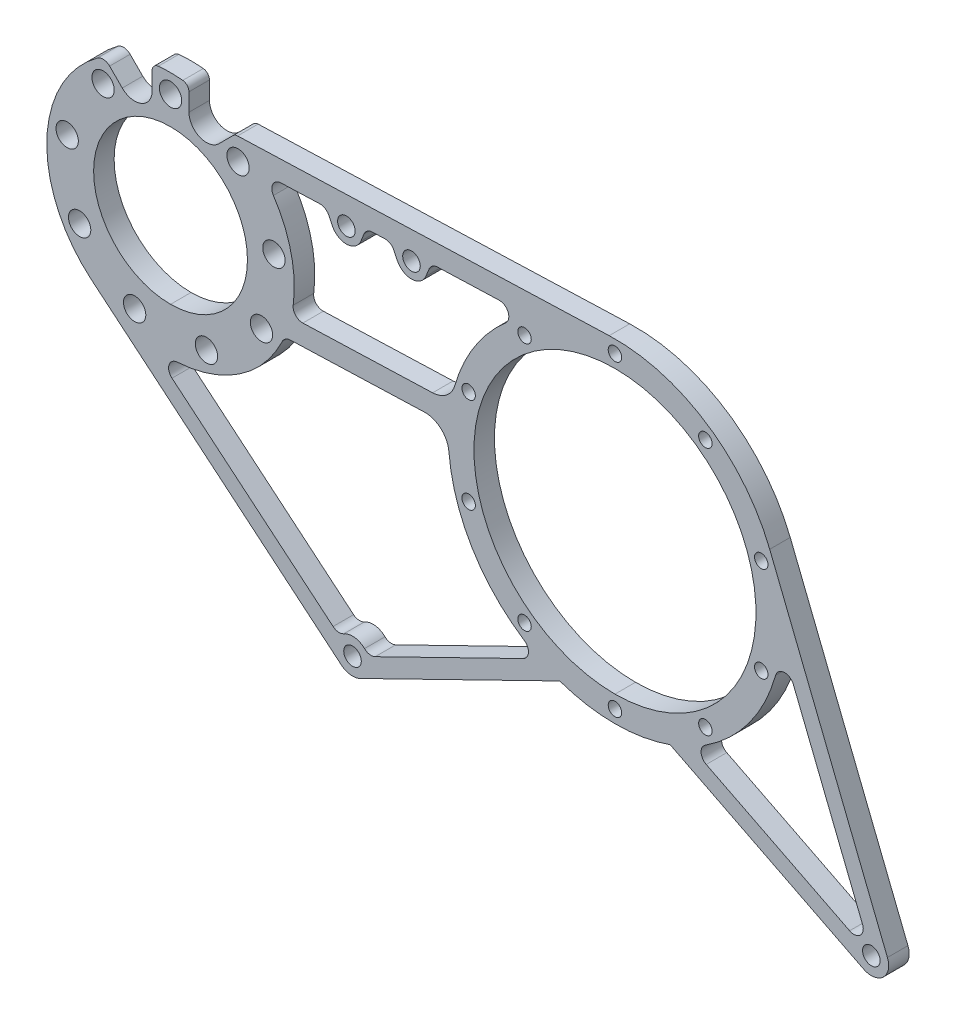
SolidWorks part; units mm, degrees
material "6061-T6 (SS)"
ref_plane "Front Plane" through (0, 0, 0) normal (0, 0, 1) x (1, 0, 0)
ref_plane "Top Plane" through (0, 0, 0) normal (0, 1, 0) x (1, 0, 0)
ref_plane "Right Plane" through (0, 0, 0) normal (1, 0, 0) x (0, 0, -1)
sketch "Sketch2" plane through (0, 0, 0) normal (0, 0, 1) x (1, 0, 0)
  line L0 (-114.3, 107.95) -> (-114.3, 95.25) construction
  line L1 (-308.8661, 91.7104) -> (-215.9264, 14.1075)
  line L3 (-13.0706, 21.4387) -> (-56.8054, 130.918)
  line L4 (-208.9705, 13.2659) -> (-134.815, 49.5352)
  line L5 (-21.9498, 13.301) -> (-93.785, 49.5352)
  line L7 (-254.4917, 165.0591) -> (-116.4363, 169.8256)
  line L10 (-286.2388, 170.2207) -> (-286.2388, 163.648)
  line L11 (-299.2388, 163.648) -> (-299.2388, 164.225)
  line L12 (-256.2001, 164.3167) -> (-261.465, 159.0518)
  line L13 (-272.5612, 163.648) -> (-272.5612, 170.2207)
  line L14 (-286.2388, 170.2207) -> (-286.2388, 163.648)
  line L16 (-256.2001, 164.3167) -> (-261.465, 159.0518)
  line L17 (-272.5612, 163.648) -> (-272.5612, 170.2207)
  line L84 (-302.5999, 164.3167) -> (-297.335, 159.0518) construction
  line L85 (-302.028, 163.7448) -> (-297.335, 159.0518)
  circle A0 centre (-279.4, 127) radius 28.575
  circle A1 centre (-114.3, 95.25) radius 36 construction
  circle A2 centre (0, 0) radius 12.7 construction
  circle A3 centre (-228.6, 0) radius 12.7 construction
  arc A5 (-134.815, 49.5352) -> (-93.785, 49.5352) centre (-114.3, 107.95) ccw
  circle A6 centre (-19.05, 19.05) radius 3.2639
  circle A7 centre (-211.7995, 19.05) radius 3.2639
  arc A8 (-215.9264, 14.1075) -> (-208.9705, 13.2659) centre (-211.7995, 19.05) ccw
  arc A9 (-21.9498, 13.301) -> (-13.0706, 21.4387) centre (-19.05, 19.05) ccw
  circle A10 centre (-114.3, 107.95) radius 52.3875
  arc A11 (-56.8054, 130.918) -> (-116.4363, 169.8256) centre (-114.3, 107.95) ccw
  arc A12 (-134.815, 49.5352) -> (-116.4363, 169.8256) centre (-114.3, 107.95) ccw construction
  arc A13 (-308.8661, 91.7104) -> (-306.5609, 164.0931) centre (-279.4, 127) cw
  arc A20 (-299.2388, 163.648) -> (-286.2388, 163.648) centre (-292.7388, 163.648) ccw
  arc A21 (-299.2388, 164.225) -> (-303.0875, 166.4019) centre (-301.7788, 164.225) ccw
  arc A22 (-303.0875, 166.4019) -> (-252.9423, 164.5979) centre (-279.4, 127) ccw
  arc A23 (-252.9423, 164.5979) -> (-256.2001, 164.3167) centre (-254.4041, 162.5207) ccw
  arc A24 (-272.5612, 163.648) -> (-261.465, 159.0518) centre (-266.0612, 163.648) ccw
  arc A25 (-272.5612, 170.2207) -> (-274.8498, 172.7483) centre (-275.1012, 170.2207) ccw
  arc A26 (-274.8498, 172.7483) -> (-283.9502, 172.7483) centre (-279.4, 127) ccw
  arc A27 (-283.9502, 172.7483) -> (-286.2388, 170.2207) centre (-283.6988, 170.2207) ccw
  arc A28 (-297.335, 159.0518) -> (-286.2388, 163.648) centre (-292.7388, 163.648) ccw
  arc A31 (-254.4917, 165.0591) -> (-256.2001, 164.3167) centre (-254.4041, 162.5207) ccw
  arc A32 (-272.5612, 163.648) -> (-261.465, 159.0518) centre (-266.0612, 163.648) ccw
  arc A33 (-272.5612, 170.2207) -> (-274.8498, 172.7483) centre (-275.1012, 170.2207) ccw
  arc A34 (-274.8498, 172.7483) -> (-283.9502, 172.7483) centre (-279.4, 127) ccw
  arc A35 (-283.9502, 172.7483) -> (-286.2388, 170.2207) centre (-283.6988, 170.2207) ccw
  arc A166 (-306.5609, 164.0931) -> (-302.028, 163.7448) centre (-304.4975, 161.2752) cw
  dimension "D1" = 25.4
  dimension "D2" = 25.4
  dimension "D8" = 57.15
  dimension "D9" = 72
  dimension "D10" = 3.4925
  dimension "D12" = 123.825
  dimension "D13" = 6.5278
  dimension "D16" = 6.5278
  dimension "D18" = 3.175
  dimension "D20" = 104.775
  dimension "D3" = 228.6
  dimension "D4" = 114.3
  dimension "D5" = 95.25
  dimension "D6" = 279.4
  dimension "D7" = 127
  dimension "D11" = 12.7
  dimension "D14" = 19.05
  dimension "D15" = 19.05
  dimension "D17" = 25.4
  dimension "D19" = 82.55
  dimension "D21" = 0
extrude "Boss-Extrude1" add sketch "Sketch2" along normal blind 7.62
sketch "Sketch3" plane through (0, 0, 7.62) normal (0, 0, 1) x (1, 0, 0)
  line L0 (-279.4, 127) -> (-279.4, 166) construction
  line L1 (-114.3, 107.95) -> (-114.3, 165.1) construction
  circle A0 centre (-279.4, 127) radius 39 construction
  circle A1 centre (-279.4, 166) radius 4.15
  circle A2 centre (-254.3313, 156.8757) radius 4.15
  circle A3 centre (-240.9925, 133.7723) radius 4.15
  circle A4 centre (-245.625, 107.5) radius 4.15
  circle A5 centre (-266.0612, 90.352) radius 4.15
  circle A6 centre (-292.7388, 90.352) radius 4.15
  circle A7 centre (-313.175, 107.5) radius 4.15
  circle A8 centre (-317.8075, 133.7723) radius 4.15
  circle A9 centre (-304.4687, 156.8757) radius 4.15
  circle A10 centre (-114.3, 107.95) radius 57.15 construction
  circle A11 centre (-114.3, 165.1) radius 2.5
  circle A12 centre (-80.7081, 154.1853) radius 2.5
  circle A13 centre (-59.9471, 125.6103) radius 2.5
  circle A14 centre (-59.9471, 90.2897) radius 2.5
  circle A15 centre (-80.7081, 61.7147) radius 2.5
  circle A16 centre (-114.3, 50.8) radius 2.5
  circle A17 centre (-147.8919, 61.7147) radius 2.5
  circle A18 centre (-168.6529, 90.2897) radius 2.5
  circle A19 centre (-168.6529, 125.6103) radius 2.5
  circle A20 centre (-147.8919, 154.1853) radius 2.5
  point P24 (-279.4, 127)
  point P48 (-114.3, 107.95)
  dimension "D1" = 78
  dimension "D2" = 8.3
  dimension "D4" = 114.3
  dimension "D5" = 5
  dimension "D3" = 9
  dimension "D6" = 10
extrude "Cut-Extrude1" cut sketch "Sketch3" against normal through all both and the other way through all
sketch "Sketch4" plane through (0, 0, 7.62) normal (0, 0, 1) x (1, 0, 0)
  line L0 (-278.8626, 74.9306) -> (-219.0181, 24.9616)
  line L1 (-48.0193, 91.8071) -> (-22.3039, 27.4349)
  line L2 (-308.8661, 91.7104) -> (-215.9264, 14.1075) construction
  line L3 (-148.3931, 49.9629) -> (-203.3792, 23.0694)
  line L4 (-208.9705, 13.2659) -> (-134.815, 49.5352) construction
  line L5 (-238.4024, 157.9901) -> (-157.3456, 160.7887)
  line L7 (-80.3879, 49.8896) -> (-27.12, 23.021)
  line L8 (-93.785, 49.5352) -> (-21.9498, 13.301) construction
  line L9 (-13.0706, 21.4387) -> (-56.8054, 130.918) construction
  line L10 (-230.2469, 116.9721) -> (-182.0371, 118.6366)
  line L11 (-234.876, 109.1877) -> (-185.1604, 110.9042)
  line L13 (-116.4363, 169.8256) -> (-254.4917, 165.0591) construction
  arc A0 (-233.8293, 120.9241) -> (-237.9076, 107.2013) centre (-279.4, 127) ccw construction
  arc A1 (-175.9949, 102.7641) -> (-173.8002, 125.0639) centre (-114.3, 107.95) ccw construction
  circle A2 centre (-19.05, 19.05) radius 6.4389 construction
  circle A3 centre (-211.7995, 19.05) radius 6.4389 construction
  arc A4 (-306.5609, 164.0931) -> (-308.8661, 91.7104) centre (-279.4, 127) ccw construction
  arc A5 (-241.1849, 152.5581) -> (-233.8293, 120.9241) centre (-279.4, 127) cw
  arc A6 (-154.933, 154.6631) -> (-173.8002, 125.0639) centre (-114.3, 107.95) ccw
  arc A7 (-54.6287, 91.4427) -> (-80.7099, 55.9417) centre (-114.3, 107.95) cw
  arc A8 (-157.3456, 160.7887) -> (-154.933, 154.6631) centre (-157.2251, 157.2982) cw
  arc A9 (-238.4024, 157.9901) -> (-241.1849, 152.5581) centre (-238.2818, 154.4997) ccw
  arc A10 (-278.8626, 74.9306) -> (-276.8202, 81.0984) centre (-276.6242, 77.6114) cw
  arc A11 (-148.0251, 56.0292) -> (-148.3931, 49.9629) centre (-149.9276, 53.1003) cw
  arc A12 (-80.3879, 49.8896) -> (-80.7099, 55.9417) centre (-78.8151, 53.0079) cw
  arc A13 (-48.0193, 91.8071) -> (-54.6287, 91.4427) centre (-51.2626, 90.5115) ccw
  arc A14 (-27.12, 23.021) -> (-22.3039, 27.4349) centre (-25.5472, 26.1393) ccw
  arc A15 (-215.0283, 24.6208) -> (-207.3352, 23.69) centre (-211.7995, 19.05) cw
  arc A16 (-203.3792, 23.0694) -> (-207.3352, 23.69) centre (-204.9137, 26.2067) cw
  arc A17 (-219.0181, 24.9616) -> (-215.0283, 24.6208) centre (-216.7797, 27.6425) ccw
  arc A18 (-237.9076, 107.2013) -> (-276.8202, 81.0984) centre (-279.4, 127) cw
  arc A19 (-175.9949, 102.7641) -> (-148.0251, 56.0292) centre (-114.3, 107.95) ccw
  arc A22 (-230.2469, 116.9721) -> (-233.8293, 120.9241) centre (-230.3674, 120.4625) cw
  arc A23 (-234.876, 109.1877) -> (-237.9076, 107.2013) centre (-234.7555, 105.6973) ccw
  arc A24 (-182.0371, 118.6366) -> (-173.8002, 125.0639) centre (-182.3438, 127.5213) ccw
  arc A25 (-185.1604, 110.9042) -> (-175.9949, 102.7641) centre (-184.8537, 102.0195) cw
  point P40 (-245.2273, 157.7545)
  point P43 (-286.9003, 81.6419)
  point P46 (-142.5125, 52.8391)
  point P50 (-52.5701, 103.1988)
  point P56 (-216.7985, 23.1083)
  dimension "D1" = 61.9125
  dimension "D2" = 12.8778
  dimension "D3" = 12.8778
  dimension "D9" = 3.4925
  dimension "D10" = 61.9125
  dimension "D11" = 3.4925
  dimension "D14" = 8.89
  dimension "D15" = 8.89
  dimension "D4" = 6.35
  dimension "D5" = 6.35
  dimension "D6" = 7.62
  dimension "D7" = 6.35
  dimension "D8" = 6.35
  dimension "D12" = 41.275
  dimension "D13" = 7.62
extrude "Cut-Extrude2" cut sketch "Sketch4" against normal through all both and the other way through all
sketch "Sketch6" plane through (0, 0, 7.62) normal (0, 0, 1) x (1, 0, 0)
  line L0 (-256.2001, 164.3171) -> (-261.465, 159.0522)
  line L1 (-272.5612, 163.6484) -> (-272.5612, 170.2212)
  line L2 (-286.2388, 170.2212) -> (-286.2388, 163.6484)
  line L3 (-299.2388, 163.6484) -> (-299.2392, 164.2676)
  arc A0 (-303.0807, 166.406) -> (-252.9493, 164.6028) centre (-279.4, 127) ccw
  arc A1 (-252.9493, 164.6028) -> (-256.2001, 164.3171) centre (-254.4043, 162.5208) ccw
  arc A2 (-272.5612, 163.6484) -> (-261.465, 159.0522) centre (-266.0612, 163.6484) ccw
  arc A3 (-272.5612, 170.2212) -> (-274.8498, 172.7487) centre (-275.1012, 170.2212) ccw
  arc A4 (-274.8498, 172.7487) -> (-283.9502, 172.7487) centre (-279.4, 127.0004) ccw
  arc A5 (-283.9502, 172.7487) -> (-286.2388, 170.2212) centre (-283.6988, 170.2212) ccw
  arc A6 (-299.2388, 163.6484) -> (-286.2388, 163.6484) centre (-292.7388, 163.6484) ccw
  arc A7 (-299.2392, 164.2676) -> (-303.0807, 166.406) centre (-301.7788, 164.225) ccw
  dimension "D1" = 45.974
  dimension "D2" = 2.54
  dimension "D4" = 6.5
  dimension "D5" = 6.5
  dimension "D6" = 2.54
  dimension "D7" = 2.54
  dimension "D8" = 45.974
  dimension "D9" = 2.54
  dimension "D3" = 7.4457
  dimension "D10" = 6.5727
ref_plane "Plane3" through (0, 0, 3.81) normal (0, 0, 1) x (1, 0, 0)
ref_axis "Axis1" through (-279.4, 127, 7.62) along (0, 0, -1)
ref_plane "Plane1" through (-279.4, 0, 0) normal (1, 0, 0) x (0, 0, -1)
ref_axis "Axis2" through (-114.3, 107.95, 7.62) along (0, 0, -1)
ref_plane "Plane2" through (-114.3, 0, 0) normal (1, 0, 0) x (0, 0, -1)
split line "Split Line1"
split line "Split Line2"
sketch "Sketch7" plane through (0, 0, 3.81) normal (0, 0, 1) x (1, 0, 0)
  arc A0 (-279.4, 155.575) -> (-279.4, 98.425) centre (-279.4, 127) ccw construction
  arc A1 (-279.4, 98.425) -> (-279.4, 155.575) centre (-279.4, 127) ccw construction
  arc A2 (-279.4, 155.575) -> (-279.4, 98.425) centre (-279.4, 127) ccw
  arc A3 (-279.4, 98.425) -> (-279.4, 155.575) centre (-279.4, 127) ccw
  arc A4 (-114.3, 55.5625) -> (-114.3, 160.3375) centre (-114.3, 107.95) ccw construction
  arc A5 (-114.3, 160.3375) -> (-114.3, 55.5625) centre (-114.3, 107.95) ccw construction
  arc A6 (-114.3, 55.5625) -> (-114.3, 160.3375) centre (-114.3, 107.95) ccw
  arc A7 (-114.3, 160.3375) -> (-114.3, 55.5625) centre (-114.3, 107.95) ccw
  point P4 (-279.4, 127)
  point P8 (-114.3, 107.95)
sketch "Sketch11" plane through (0, 0, 0) normal (0, 0, -1) x (-1, 0, 0)
  line L0 (157.3456, 160.7887) -> (238.4024, 157.9901) construction
  line L1 (182.3987, 159.9237) -> (187.9461, 159.7321)
  line L2 (184.5049, 154.9364) -> (183.3433, 157.8152)
  line L3 (189.8872, 157.1081) -> (189.9754, 159.6621) construction
  line L4 (195.1068, 154.5703) -> (196.4642, 157.3621)
  line L5 (201.9791, 156.6907) -> (202.2057, 163.2538) construction
  line L6 (189.8872, 157.1081) -> (214.071, 156.2732) construction
  line L7 (208.6887, 154.1014) -> (207.5271, 156.9802)
  line L8 (214.071, 156.2732) -> (214.1591, 158.8271)
  line L9 (219.2906, 153.7354) -> (220.648, 156.5272)
  line L10 (221.7357, 158.5656) -> (206.5825, 159.0887)
  line L11 (223.9095, 158.4905) -> (221.7357, 158.5656)
  line L12 (197.552, 159.4005) -> (199.7256, 159.3254)
  line L13 (206.5825, 159.0887) -> (204.4088, 159.1638)
  line L14 (182.3987, 159.9237) -> (180.2251, 159.9987)
  line L15 (192.0046, 159.592) -> (197.552, 159.4005)
  arc A0 (187.9461, 159.7321) -> (192.0046, 159.592) centre (189.8872, 157.1081) ccw
  circle A1 centre (214.071, 156.2732) radius 3.3 construction
  arc A2 (184.5049, 154.9364) -> (195.1068, 154.5703) centre (189.8872, 157.1081) ccw
  circle A4 centre (189.8872, 157.1081) radius 5.8039 construction
  circle A5 centre (189.8872, 157.1081) radius 3.2639 construction
  arc A6 (219.2906, 153.7354) -> (208.6887, 154.1014) centre (214.071, 156.2732) cw
  arc A7 (216.1884, 158.7571) -> (212.1299, 158.8972) centre (214.071, 156.2732) cw
  arc A8 (183.3433, 157.8152) -> (180.2251, 159.9987) centre (180.1045, 156.5083) ccw
  arc A9 (223.9095, 158.4905) -> (220.648, 156.5272) centre (223.7889, 155.0001) ccw
  arc A10 (207.5271, 156.9802) -> (204.4088, 159.1638) centre (204.2883, 155.6733) ccw
  arc A11 (199.7256, 159.3254) -> (196.4642, 157.3621) centre (199.6051, 155.835) ccw
  dimension "D1" = 6.5278
  dimension "D3" = 3.4925
  dimension "D2" = 2.54
extrude "Boss-Extrude2" add sketch "Sketch11" against normal up to surface (7.62 mm away) contours A10 L7 A6 L9 A9 L11 L10 A7 L13 | A11 L12 L15 A0 L1 L14 A8 L2 A2 L4 region at (-185.1651, 159.6145, 0) region at (-208.3059, 155.6207, 0)
sketch "Sketch12" plane through (0, 0, 0) normal (0, 0, -1) x (-1, 0, 0)
  circle A1 centre (189.8872, 157.1081) radius 3.2639
  circle A2 centre (214.071, 156.2732) radius 3.2639
extrude "Cut-Extrude3" cut sketch "Sketch12" against normal through all both and the other way through all
